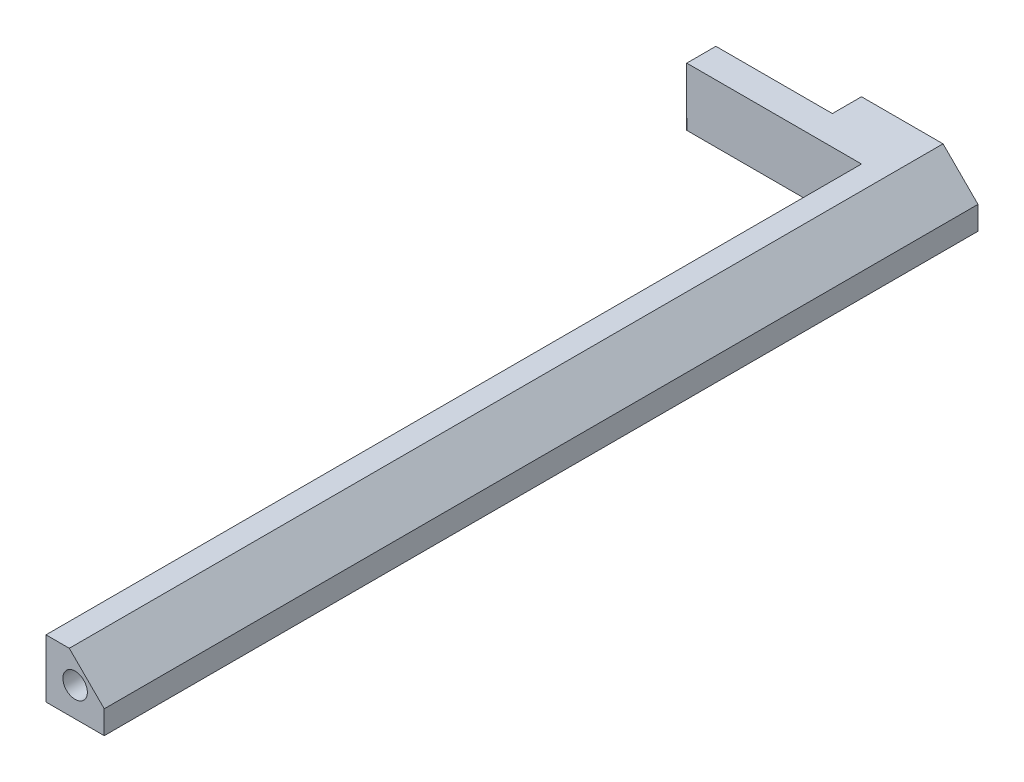
SolidWorks part; units mm, degrees
material "ABS"
ref_plane "Płaszczyzna przednia" through (0, 0, 0) normal (0, 0, 1) x (1, 0, 0)
ref_plane "Płaszczyzna górna" through (0, 0, 0) normal (0, 1, 0) x (1, 0, 0)
ref_plane "Płaszczyzna prawa" through (0, 0, 0) normal (1, 0, 0) x (0, 0, -1)
sketch "Szkic1" plane through (0, 0, 0) normal (0, 1, 0) x (1, 0, 0)
  line L0 (0, 0) -> (0, 150)
  line L1 (0, 150) -> (-20, 150)
  line L2 (-20, 150) -> (-20, 145)
  line L5 (-40, 140) -> (-10, 140)
  line L6 (-10, 140) -> (-10, 0)
  line L7 (-10, 0) -> (0, 0)
  line L8 (-40, 140) -> (-40, 145)
  line L9 (-40, 145) -> (-20, 145)
  dimension "D1" = 5
  dimension "D2" = 20
  dimension "D3" = 20
  dimension "D4" = 5
  dimension "D5" = 10
  dimension "D6" = 140
extrude "Dodanie-wyciągnięcie1" add sketch "Szkic1" along normal blind 10
sketch "Szkic2" plane through (0, 0, 0) normal (0, -1, 0) x (1, 0, 0)
  line L0 (0, 0) -> (0, -27) construction
  line L1 (0, 0) -> (0, -150) construction
  line L2 (0, -27) -> (-7.2, -27) construction
  line L3 (-7.2, -27) -> (-7.2, -123) construction
  circle A0 centre (-7.2, -123) radius 2.1
  circle A1 centre (-7.2, -27) radius 2.1
  dimension "D4" = 4.2
  dimension "D5" = 4.2
  dimension "D1" = 27
  dimension "D2" = 7.2
  dimension "D3" = 96
extrude "Wytnij-wyciągnięcie1" cut sketch "Szkic2" against normal blind 4
sketch "Szkic3" plane through (0, 0, 0) normal (0, 0, 1) x (1, 0, 0)
  line L0 (0, 0) -> (-5, 0) construction
  line L1 (-10, 0) -> (0, 0) construction
  line L2 (-5, 0) -> (-5, 5) construction
  circle A0 centre (-5, 5) radius 2.1
  dimension "D3" = 4.2
  dimension "D1" = 5
  dimension "D2" = 5
extrude "Wytnij-wyciągnięcie2" cut sketch "Szkic3" against normal blind 4
chamfer "Sfazowanie1" distance 6 angle 45 1 edges at (0, 10, -75)
